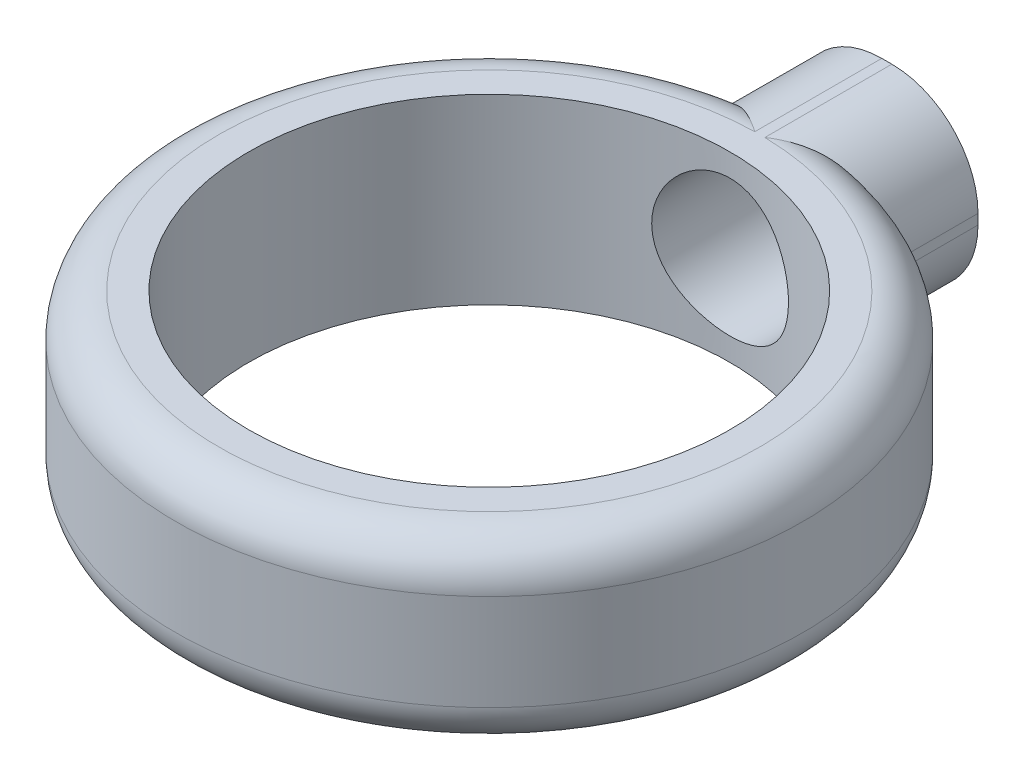
SolidWorks part; units mm, degrees
ref_plane "Front Plane" through (0, 0, 0) normal (0, 0, 1) x (1, 0, 0)
ref_plane "Top Plane" through (0, 0, 0) normal (0, 1, 0) x (1, 0, 0)
ref_plane "Right Plane" through (0, 0, 0) normal (1, 0, 0) x (0, 0, -1)
sketch "Sketch1" plane through (0, 0, 0) normal (0, 1, 0) x (1, 0, 0)
  line L0 (-6.35, 27.686) -> (-6.35, 20.9007)
  line L1 (6.35, 20.9007) -> (6.35, 27.686)
  line L2 (6.35, 27.686) -> (-6.35, 27.686)
  circle A0 centre (0, 0) radius 16.764
  arc A1 (-6.35, 20.9007) -> (6.35, 20.9007) centre (0, 0) ccw
  point P5 (0, 27.686)
  dimension "D1" = 33.528
  dimension "D2" = 5.08
  dimension "D3" = 12.7
  dimension "D4" = 27.686
extrude "Boss-Extrude1" add sketch "Sketch1" along normal blind 12.7
fillet "Fillet1" radius 3 2 edges at (0, 0, 21.844) (0, 12.7, 21.844)
fillet "Fillet3" radius 6 4 edges at (-6.35, 0, -22.7139) (-6.35, 12.7, -22.7139) (6.35, 12.7, -22.7139) (6.35, 0, -22.7139)
sketch "Sketch2" plane through (0, 0, -27.686) normal (0, 0, -1) x (-1, 0, 0)
  line L0 (-0.35, 12.7) -> (0.35, 12.7) construction
  line L1 (0, 12.7) -> (0, 0) construction
  circle A0 centre (0, 6.35) radius 4.7625
  point P8 (0, 6.35)
  dimension "D1" = 9.525
extrude "Cut-Extrude1" cut sketch "Sketch2" against normal up to next
